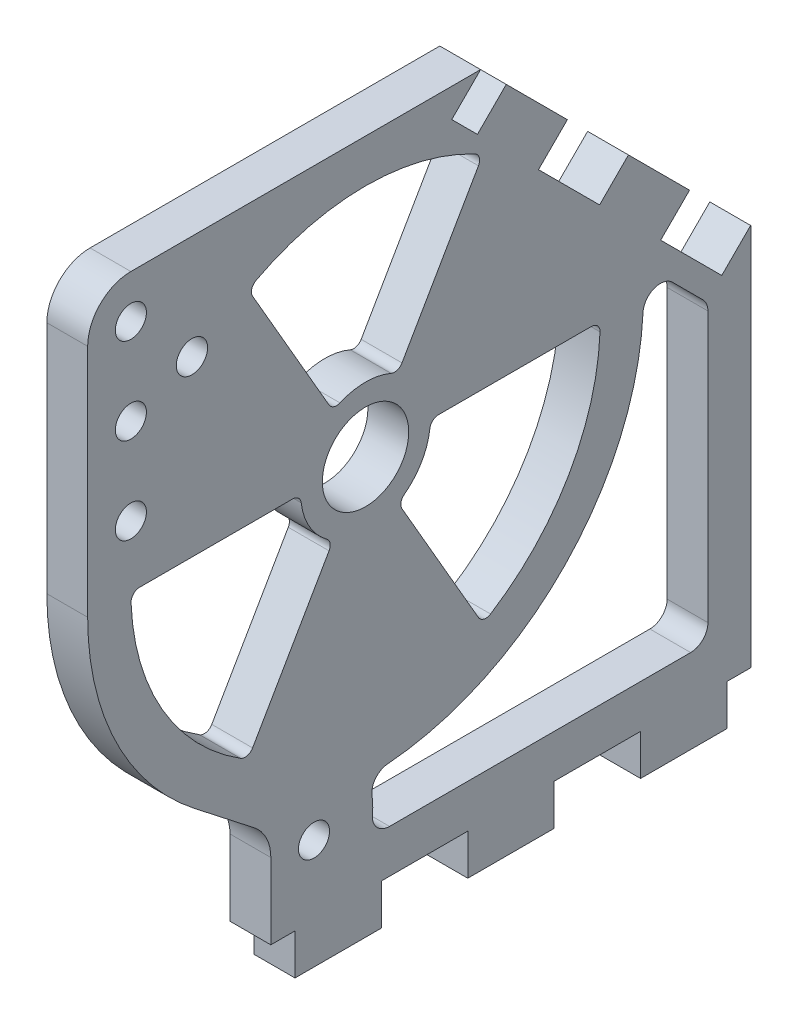
SolidWorks part; units mm, degrees
material "Custom Plastic"
ref_plane "Front Plane" through (0, 0, 0) normal (0, 0, 1) x (1, 0, 0)
ref_plane "Top Plane" through (0, 0, 0) normal (0, 1, 0) x (1, 0, 0)
ref_plane "Right Plane" through (0, 0, 0) normal (1, 0, 0) x (0, 0, -1)
sketch "Sketch2" plane through (0, 0, 0) normal (1, 0, 0) x (0, 0, -1)
  line L0 (-28.956, 10.16) -> (-35.306, 10.16) construction
  line L1 (-35.306, 0) -> (-35.306, 14.2168)
  line L2 (-35.306, 14.2168) -> (-46.5136, 22.9635)
  line L4 (-55.88, 89.662) -> (-55.88, 76.962) construction
  line L5 (-35.306, 0) -> (35.306, 0)
  line L6 (-62.23, 96.012) -> (-62.23, 55.1649)
  line L7 (-55.88, 76.962) -> (-55.88, 64.262) construction
  line L10 (-62.23, 96.012) -> (-4.4635, 96.012)
  line L11 (-55.88, 89.662) -> (-55.88, 96.012) construction
  line L12 (-55.88, 89.662) -> (-62.23, 89.662) construction
  line L24 (-4.4635, 96.012) -> (35.306, 56.2425)
  line L25 (35.306, 56.2425) -> (35.306, 0)
  circle A0 centre (-55.88, 89.662) radius 2.286
  circle A1 centre (-28.956, 10.16) radius 2.286
  circle A2 centre (-55.88, 89.662) radius 87.503 construction
  circle A3 centre (-28.956, 10.16) radius 126.6734 construction
  circle A4 centre (-21.3829, 55.1649) radius 40.8471 construction
  circle A5 centre (-55.88, 76.962) radius 2.286
  circle A6 centre (-55.88, 64.262) radius 2.286
  arc A7 (-62.23, 55.1649) -> (-46.5136, 22.9635) centre (-21.3829, 55.1649) ccw
  point P0 (0, 0)
  point P1 (-55.88, 89.662)
  point P3 (-28.956, 10.16)
  point P34 (0, 0)
  dimension "D4" = 45
  dimension "D16" = 253.3467
  dimension "D19" = 175.006
  dimension "D2" = 4.572
  dimension "D3" = 6.35
  dimension "D5" = 12.7
  dimension "D14" = 28.956
  dimension "D15" = 10.16
  dimension "D17" = 89.662
  dimension "D18" = 55.88
extrude "Main" add sketch "Sketch2" along normal blind 6 contours A1 A0 region at (0, 47.4384, 13.2547)
sketch "Sketch3" plane through (6, 0, 0) normal (1, 0, 0) x (0, 0, -1)
  line L0 (-6.35, -6) -> (6.35, -6)
  line L1 (-31.75, 0) -> (-19.05, 0)
  line L2 (-31.75, 0) -> (-31.75, -6)
  line L3 (-31.75, -6) -> (-19.05, -6)
  line L4 (-19.05, 0) -> (-19.05, -6)
  line L5 (6.35, 0) -> (6.35, -6)
  line L6 (-6.35, 0) -> (6.35, 0)
  line L7 (-6.35, 0) -> (-6.35, -6)
  line L8 (19.05, -6) -> (31.75, -6)
  line L9 (31.75, 0) -> (31.75, -6)
  line L10 (19.05, 0) -> (31.75, 0)
  line L11 (19.05, 0) -> (19.05, -6)
  line L12 (-31.75, -6) -> (-6.35, -6) construction
  line L13 (-35.306, 0) -> (35.306, 0) construction
  dimension "D1" = 12.7
  dimension "D2" = 6
  dimension "D4" = 25.4
  dimension "D3" = 3
extrude "plate mount 1" add sketch "Sketch3" against normal through all
sketch "Sketch4" plane through (0, 0, 0) normal (-1, 0, 0) x (0, 0, 1)
  line L0 (4.4635, 96.012) -> (0.6918, 92.2403) construction
  line L1 (0.6918, 92.2403) -> (4.9344, 87.9977) construction
  line L2 (4.9344, 87.9977) -> (8.7061, 91.7694) construction
  line L3 (8.7061, 91.7694) -> (4.4635, 96.012) construction
  line L4 (-13.0261, 70.0371) -> (-4.0459, 79.0174) construction
  line L5 (-4.0459, 79.0174) -> (-8.2885, 83.26) construction
  line L6 (-8.2885, 83.26) -> (-17.2687, 74.2798) construction
  line L7 (-17.2687, 74.2798) -> (-13.0261, 70.0371) construction
  line L8 (-30.9866, 52.0766) -> (-22.0064, 61.0569) construction
  line L9 (-22.0064, 61.0569) -> (-26.249, 65.2995) construction
  line L10 (-26.249, 65.2995) -> (-35.2293, 56.3193) construction
  line L11 (-35.2293, 56.3193) -> (-30.9866, 52.0766) construction
  line L12 (4.4635, 96.012) -> (0.6918, 92.2403)
  line L13 (0.6918, 92.2403) -> (4.9344, 87.9977)
  line L14 (4.9344, 87.9977) -> (8.7061, 91.7694)
  line L15 (8.7061, 91.7694) -> (4.4635, 96.012)
  line L16 (-13.0261, 70.0371) -> (-4.0459, 79.0174)
  line L17 (-4.0459, 79.0174) -> (-8.2885, 83.26)
  line L18 (-8.2885, 83.26) -> (-17.2687, 74.2798)
  line L19 (-17.2687, 74.2798) -> (-13.0261, 70.0371)
  line L20 (-30.9866, 52.0766) -> (-22.0064, 61.0569)
  line L21 (-22.0064, 61.0569) -> (-26.249, 65.2995)
  line L22 (-26.249, 65.2995) -> (-35.2293, 56.3193)
  line L23 (-35.2293, 56.3193) -> (-30.9866, 52.0766)
extrude "plate mount 2" cut sketch "Sketch4" against normal through all
sketch "Sketch5" plane through (6, 0, 0) normal (1, 0, 0) x (0, 0, -1)
  line L0 (-55.88, 89.662) -> (-46.8997, 80.6817) construction
  line L1 (-46.8997, 80.6817) -> (-62.23, 80.6817) construction
  line L2 (-62.23, 96.012) -> (-62.23, 55.1649) construction
  circle A0 centre (-46.8997, 80.6817) radius 2.3026
  arc A1 (-63.232, 82.31) -> (-48.528, 82.31) centre (-55.88, 89.662) ccw construction
  arc A39 (-66.4885, 79.0535) -> (-45.2715, 79.0535) centre (-55.88, 89.662) ccw construction
  dimension "D1" = 45
extrude "pot mount hole" cut sketch "Sketch5" against normal through all
sketch "Sketch6" plane through (6, 0, 0) normal (1, 0, 0) x (0, 0, -1)
  line L1 (-4.1343, 85.0403) -> (-21.3829, 55.1649) construction
  line L2 (-21.3829, 55.1649) -> (-38.6314, 25.2895) construction
  line L3 (-55.88, 55.1649) -> (-21.3829, 55.1649) construction
  line L4 (-21.3829, 55.1649) -> (13.1142, 55.1649) construction
  line L5 (-4.1343, 25.2895) -> (-21.3829, 55.1649) construction
  line L6 (-21.3829, 55.1649) -> (-38.6314, 85.0403) construction
  line L7 (-55.88, 55.1649) -> (-38.6314, 85.0403) construction
  line L8 (-38.6314, 85.0403) -> (-4.1343, 85.0403) construction
  line L9 (-4.1343, 85.0403) -> (13.1142, 55.1649) construction
  line L10 (13.1142, 55.1649) -> (-4.1343, 25.2895) construction
  line L11 (-4.1343, 25.2895) -> (-38.6314, 25.2895) construction
  line L12 (-38.6314, 25.2895) -> (-55.88, 55.1649) construction
  line L13 (-30.9079, 55.1649) -> (-55.88, 55.1649)
  line L14 (-26.1454, 46.916) -> (-38.6314, 25.2895)
  line L15 (-16.6204, 46.916) -> (-4.1343, 25.2895)
  line L16 (-11.8579, 55.1649) -> (13.1142, 55.1649)
  line L17 (-16.6204, 63.4138) -> (-4.1343, 85.0403)
  line L18 (-26.1454, 63.4138) -> (-38.6314, 85.0403)
  circle A0 centre (-21.3829, 55.1649) radius 34.4971 construction
  arc A1 (-62.23, 55.1649) -> (-46.5136, 22.9635) centre (-21.3829, 55.1649) ccw construction
  arc A2 (-62.23, 55.1649) -> (-46.5136, 22.9635) centre (-21.3829, 55.1649) ccw construction
  circle A3 centre (-21.3829, 55.1649) radius 6.35
  arc A4 (-26.1454, 63.4138) -> (-16.6204, 63.4138) centre (-21.3829, 55.1649) cw
  arc A5 (-11.8579, 55.1649) -> (-16.6204, 46.916) centre (-21.3829, 55.1649) cw
  arc A6 (-30.9079, 55.1649) -> (-26.1454, 46.916) centre (-21.3829, 55.1649) ccw
  arc A7 (-55.88, 55.1649) -> (-38.6314, 25.2895) centre (-21.3829, 55.1649) ccw
  arc A8 (13.1142, 55.1649) -> (-4.1343, 25.2895) centre (-21.3829, 55.1649) cw
  arc A9 (-38.6314, 85.0403) -> (-4.1343, 85.0403) centre (-21.3829, 55.1649) cw
  dimension "D1" = 6.35
  dimension "D2" = 3.175
  dimension "D3" = 12.7
extrude "radioactive" cut sketch "Sketch6" against normal through all contours L13 A7 L14 A6 | A8 L16 A5 L15 | A9 L18 A4 L17 | A3 region at (6, 43.5281, 41.5384) region at (6, 43.5281, 1.2274) region at (6, 78.4385, 21.3829)
fillet "radioactive  fillet" radius 1.27 12 edges at (3, 63.4138, 26.1454) (3, 63.4138, 16.6204) (3, 55.1649, 30.9079) (3, 46.916, 26.1454) (3, 46.916, 16.6204) (3, 55.1649, 11.8579) (3, 25.2895, 38.6314) (3, 25.2895, 4.1343) (3, 85.0403, 4.1343) (3, 55.1649, -13.1142) (3, 85.0403, 38.6314) (3, 55.1649, 55.88)
sketch "Sketch7" plane through (6, 0, 0) normal (1, 0, 0) x (0, 0, -1)
  line L0 (-28.956, 15.026) -> (-28.956, 6.35) construction
  line L1 (-28.956, 6.35) -> (28.956, 6.35) construction
  line L2 (28.956, 6.35) -> (28.956, 49.6171) construction
  line L3 (28.956, 49.6171) -> (19.2522, 59.3209) construction
  line L4 (17.2687, 74.2798) -> (26.249, 65.2995) construction
  line L5 (35.306, 56.2425) -> (35.306, 0) construction
  line L6 (6.35, 0) -> (19.05, 0) construction
  line L7 (-35.306, 0) -> (-35.306, 14.2168) construction
  line L8 (-19.05, 0) -> (-6.35, 0) construction
  line L9 (30.9866, 52.0766) -> (22.0064, 61.0569) construction
  line L10 (19.2522, 59.3209) -> (28.956, 49.6171)
  line L11 (28.956, 49.6171) -> (28.956, 6.35)
  line L12 (28.956, 6.35) -> (-21.2021, 6.35)
  circle A0 centre (-21.3829, 55.1649) radius 40.8471 construction
  arc A1 (-62.23, 55.1649) -> (-46.5136, 22.9635) centre (-21.3829, 55.1649) ccw construction
  circle A2 centre (-28.956, 10.16) radius 8.636 construction
  circle A4 centre (-28.956, 10.16) radius 2.286 construction
  arc A5 (-21.3829, 14.3178) -> (-21.2021, 6.35) centre (-28.956, 10.16) cw
  arc A6 (-21.3829, 14.3178) -> (19.2522, 59.3209) centre (-21.3829, 55.1649) ccw
  point P21 (26.4965, 56.5668)
  dimension "D5" = 6.35
  dimension "D1" = 6.35
  dimension "D2" = 6.35
  dimension "D3" = 6.35
  dimension "D4" = 3.175
extrude "Cut-Extrude4" cut sketch "Sketch7" against normal through all contours A6 A5 L12 L11 L10 region at (6, 22.5677, -12.7758)
fillet "Fillet2" radius 6.35 2 edges at (3, 14.2168, 35.306) (3, 96.012, 62.23)
fillet "Fillet3" radius 2.54 5 edges at (3, 6.35, 21.2021) (3, 6.35, -28.956) (3, 49.6171, -28.956) (3, 59.3209, -19.2522) (3, 14.3178, 21.3829)
